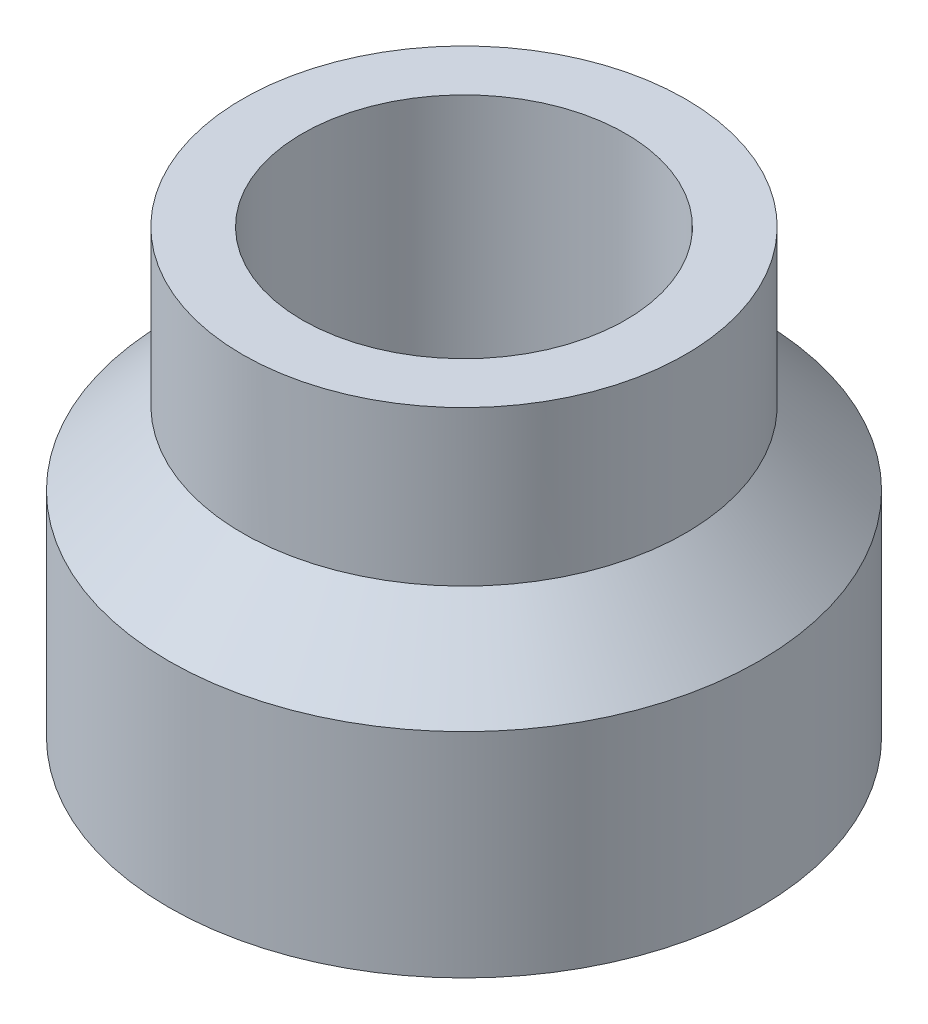
SolidWorks part; units mm, degrees
ref_plane "Front Plane" through (0, 0, 0) normal (0, 0, 1) x (1, 0, 0)
ref_plane "Top Plane" through (0, 0, 0) normal (0, 1, 0) x (1, 0, 0)
ref_plane "Right Plane" through (0, 0, 0) normal (1, 0, 0) x (0, 0, -1)
sketch "Sketch1" plane through (0, 0, 0) normal (0, 1, 0) x (1, 0, 0)
  circle A0 centre (0, 0) radius 3.475
  circle A1 centre (0, 0) radius 4.7625
  circle A2 centre (0, 0) radius 6.35
extrude "Boss-Extrude1" add sketch "Sketch1" along normal blind 3.175 contours A2 A1 region at (-6.1704, 0, 0)
extrude "Boss-Extrude2" add sketch "Sketch1<3>" along normal blind 9.5 contours A1 A0 region at (-4.6278, 0, 0)
sketch "Sketch1<3>" plane through (0, 0, 0) normal (0, 1, 0) x (1, 0, 0) same geometry as "Sketch1"
chamfer "Chamfer1" distance 3 angle 45 1 edges at (0, 3.175, 4.7625)
